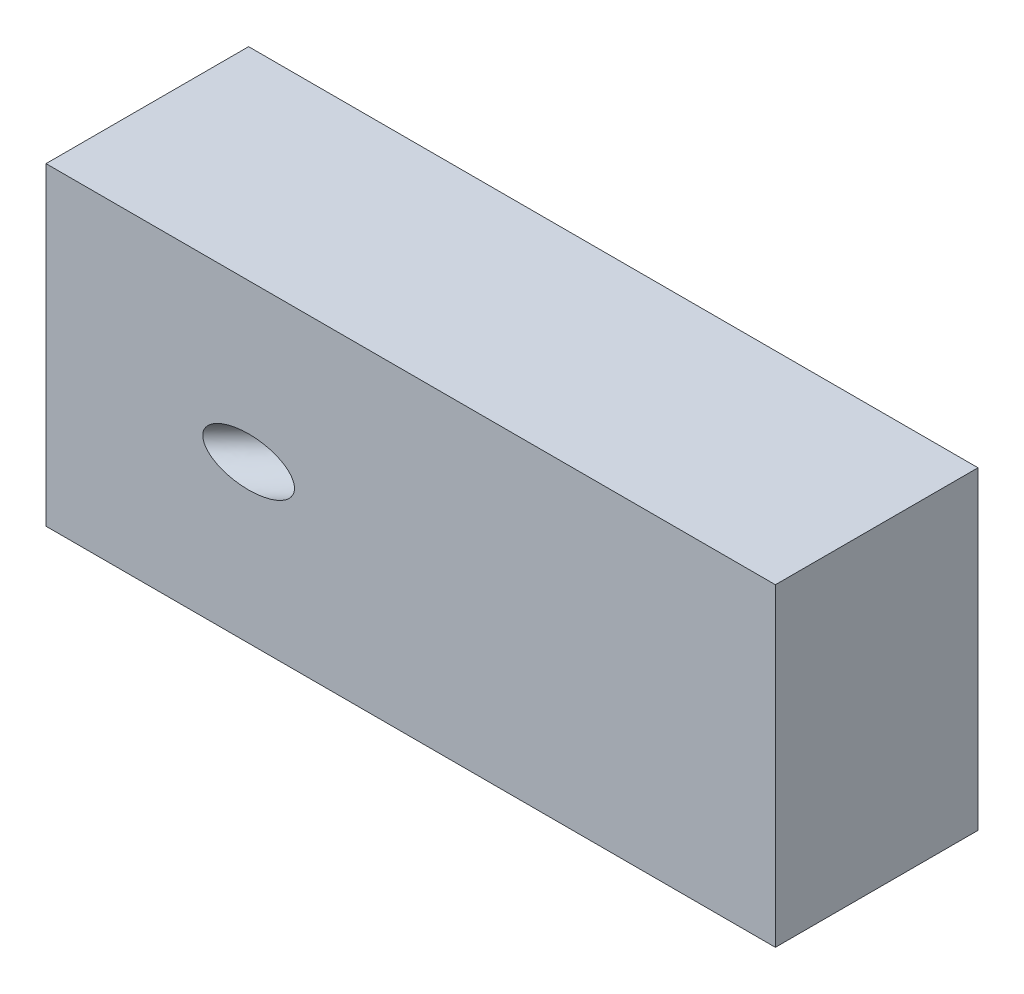
SolidWorks part; units mm, degrees
ref_plane "Plan de face" through (0, 0, 0) normal (0, 0, 1) x (1, 0, 0)
ref_plane "Plan de dessus" through (0, 0, 0) normal (0, 1, 0) x (1, 0, 0)
ref_plane "Plan de droite" through (0, 0, 0) normal (1, 0, 0) x (0, 0, -1)
sketch "Esquisse1" plane through (0, 0, 0) normal (0, 0, 1) x (1, 0, 0)
  line L1 (0, 7.75) -> (18, 7.75)
  line L2 (0, 7.75) -> (0, 0)
  line L3 (0, 0) -> (18, 0)
  line L4 (18, 7.75) -> (18, 0)
  dimension "D1" = 18
  dimension "D2" = 7.75
extrude "Boss.-Extru.1" add sketch "Esquisse1" along normal blind 5
ref_plane "Plan Milieu" through (0, 3.875, 0) normal (0, -1, 0) x (-1, 0, 0)
sketch "Esquisse10" plane through (0, 0, 5) normal (0, 0, 1) x (1, 0, 0)
  line L0 (-2.75, 3.875) -> (2.75, 3.875) construction
  line L1 (0, 7.75) -> (0, 0) construction
  point P0 (5, 3.875)
  dimension "D1" = 5
sketch "Esquisse11" plane through (0, 0, 0) normal (0, 0, -1) x (-1, 0, 0)
  line L0 (-2.75, 3.875) -> (2.75, 3.875) construction
  line L1 (0, 7.75) -> (0, 0) construction
  point P0 (-10, 3.875)
  dimension "D1" = 10
ref_axis "Axe3" through (5, 3.875, 5) along (0.7071, 0, -0.7071)
ref_axis "Axe5" [suppressed] through (5, 3.75, 5) along (0, 0, -1)
ref_plane "Plan2" through (5, 3.875, 5) normal (0.7071, 0, -0.7071) x (-0.7071, 0, -0.7071)
sketch "Esquisse13" plane through (5, 3.875, 5) normal (0.7071, 0, -0.7071) x (-0.7071, 0, -0.7071)
  ellipse E0 centre (0, 0) end of major axis (0.8, 0) minor radius 0.6
  dimension "D1" = 1.2
  dimension "D2" = 1.6
extrude "Enlèv. mat.-Extru.1" cut sketch "Esquisse13" along normal blind 15 and the other way blind 10
sketch "Esquisse15" plane through (0, 0, 0) normal (0, 0, -1) x (-1, 0, 0)
  line L0 (-18, 1.875) -> (-11.4792, 1.875) construction
  line L1 (-11.4792, 1.875) -> (-11.4792, 3.875) construction
  line L2 (-11.4792, 3.875) -> (-18, 3.875) construction
  line L3 (0, 0) -> (-18, 0) construction
  line L4 (-18, 0) -> (-18, 7.75) construction
  line L7 (-11.4792, 3.875) -> (-11.4792, 5.875) construction
  line L8 (-11.4792, 5.875) -> (-18, 5.875) construction
  circle A0 centre (-11.9792, 2.375) radius 0.5
  circle A1 centre (-11.9792, 5.375) radius 0.5
  point P13 (0, 0)
  point P14 (0, 0)
  point P16 (0, 0)
  point P17 (0, 0)
  dimension "D1" = 0.5
  dimension "D2" = 0.5
  dimension "D3" = 0.5
  dimension "D4" = 0.5
extrude "Boss.-Extru.3" add sketch "Esquisse15" along normal blind 0.55
sketch "Esquisse16" plane through (0, 0, 0) normal (0, 0, -1) x (-1, 0, 0)
  line L0 (-11.9792, 2.375) -> (-11.9792, 5.375) construction
  line L1 (-12.4792, 2.375) -> (-12.4792, 5.375)
  line L2 (-11.4792, 2.375) -> (-11.4792, 5.375)
  arc A0 (-12.4792, 2.375) -> (-11.4792, 2.375) centre (-11.9792, 2.375) ccw
  arc A1 (-11.4792, 5.375) -> (-12.4792, 5.375) centre (-11.9792, 5.375) ccw
  circle A3 centre (-11.9792, 5.375) radius 0.5 construction
  point P2 (-11.9792, 3.875)
  point P7 (0, 0)
  point P8 (0, 0)
  point P10 (0, 0)
  point P13 (0, 0)
  point P16 (0, 0)
extrude "Boss.-Extru.4" add sketch "Esquisse16" along normal blind 1.1 contours L2 A1 L1 A0
